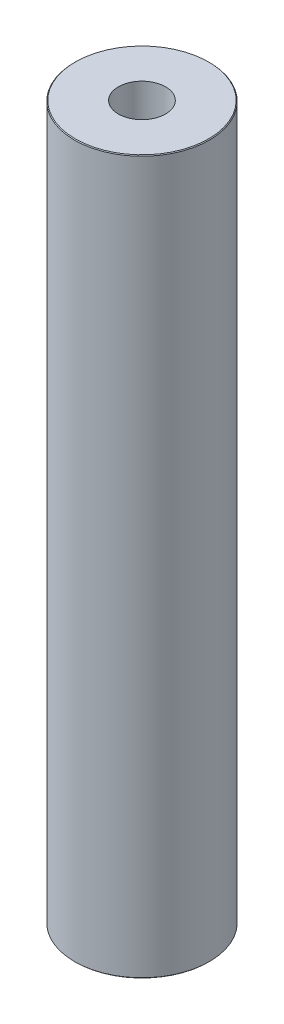
SolidWorks part; units mm, degrees
ref_plane "Front Plane" through (0, 0, 0) normal (0, 0, 1) x (1, 0, 0)
ref_plane "Top Plane" through (0, 0, 0) normal (0, 1, 0) x (1, 0, 0)
ref_plane "Right Plane" through (0, 0, 0) normal (1, 0, 0) x (0, 0, -1)
sketch "Sketch1" plane through (0, 0, 0) normal (0, 1, 0) x (1, 0, 0)
  circle A0 centre (0, 0) radius 42.5
  dimension "SHAFT_OD" = 85
extrude "Boss-Extrude1" add sketch "Sketch1" along normal blind 449.6733
sketch "Sketch2" plane through (0, 0, 0) normal (0, 1, 0) x (1, 0, 0)
  circle A0 centre (0, 0) radius 14.8944
  dimension "BORE_D" = 29.7888
extrude "Cut-Extrude1" cut sketch "Sketch2" along normal through all
chamfer "Chamfer1" distance 0.4666 angle 45 2 edges at (0, 449.6733, 42.5) (0, 0, 42.5)
